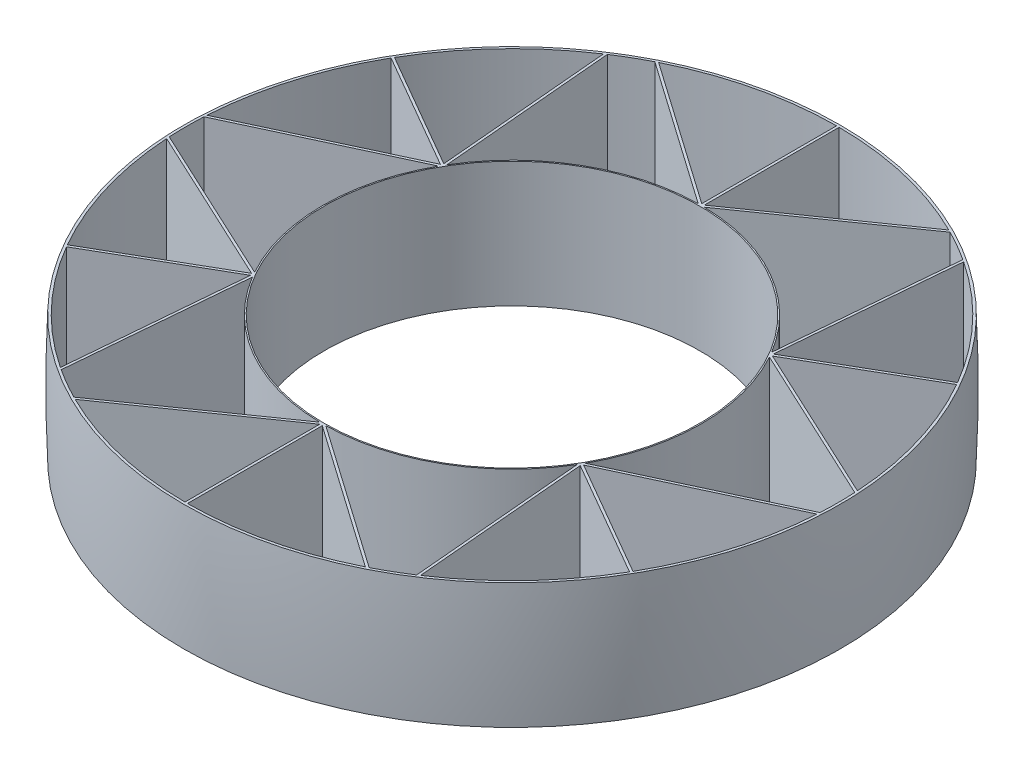
SolidWorks part; units mm, degrees
material "Бутил"
ref_plane "Спереди" through (0, 0, 0) normal (0, 0, 1) x (1, 0, 0)
ref_plane "Сверху" through (0, 0, 0) normal (0, 1, 0) x (1, 0, 0)
ref_plane "Справа" through (0, 0, 0) normal (1, 0, 0) x (0, 0, -1)
sketch "Эскиз3" plane through (0, 0, 0) normal (0, 1, 0) x (1, 0, 0)
  circle A0 centre (0, 0) radius 130
  circle A1 centre (0, 0) radius 131
  dimension "D1" = 262
  dimension "D2" = 260
sketch "Эскиз6" plane through (0, 0, 0) normal (0, 1, 0) x (1, 0, 0)
  circle A0 centre (0, 0) radius 75
  circle A1 centre (0, 0) radius 75.5
  dimension "D1" = 150
  dimension "D2" = 151
extrude "Бобышка-Вытянуть9" add sketch "Эскиз6" along normal blind 50 contours A1 A0 region at (-75.2865, 0, 0)
extrude "Бобышка-Вытянуть10" add sketch "Эскиз3" along normal up to surface (50 mm away) up to face at (0, 50, 75)
sketch "Эскиз7" plane through (0, 0, 0) normal (0, 1, 0) x (1, 0, 0)
  line L1 (-0.5, -75.4983) -> (-0.5, -129.999)
  line L2 (0.5, -75.4983) -> (0.5, -129.999)
  line L3 (0, -130) -> (0, 0) construction
  circle A0 centre (0, 0) radius 75.5 construction
  arc A2 (-0.5, -75.4983) -> (0.5, -75.4983) centre (0, -48.3147) ccw
  arc A3 (-0.5, -129.999) -> (0.5, -129.999) centre (0, 0) ccw
  circle A5 centre (0, 0) radius 130 construction
  point P1 (0, -75.5029)
  dimension "D4" = 27.1883
  dimension "D1" = 1
extrude "Бобышка-Вытянуть11" add sketch "Эскиз7" along normal up to surface (50 mm away) up to face at (0, 50, 75)
sketch "Эскиз4" plane through (0, 0, 0) normal (0, -1, 0) x (1, 0, 0)
  line L2 (-58.899, 115.8918) -> (-1.2, 75.4905)
  line L4 (0.5, 129.999) -> (0.5, 75.4983) construction
  line L6 (0, 148.9306) -> (0, 117.9564) construction
  line L7 (58.899, 115.8918) -> (1.2, 75.4905)
  line L8 (0.5, 76.1983) -> (57.9032, 116.3925)
  line L9 (0.5, 75.4983) -> (0.5, 76.1983)
  line L10 (-0.5, 76.1983) -> (-57.9032, 116.3925)
  line L11 (-0.5, 75.4983) -> (-0.5, 76.1983)
  circle A0 centre (0, 0) radius 130 construction
  arc A4 (1.2, 75.4905) -> (0.5, 75.4983) centre (0, 0) ccw
  arc A5 (57.9032, 116.3925) -> (58.899, 115.8918) centre (0, 0) cw
  circle A6 centre (0, 0) radius 75.5 construction
  arc A7 (-0.5, 129.999) -> (0.5, 129.999) centre (0, 0) ccw construction
  arc A8 (-57.9032, 116.3925) -> (-58.899, 115.8918) centre (0, 0) ccw
  arc A9 (-1.2, 75.4905) -> (-0.5, 75.4983) centre (0, 0) cw
  point P2 (0, 0)
  dimension "D1" = 110
  dimension "D5" = 0.7
  dimension "D6" = 0.7
extrude "Бобышка-Вытянуть12" add sketch "Эскиз4" against normal up to surface (50 mm away) up to face at (0, 50, 75)
sketch "Эскиз5" plane through (0, 0, 0) normal (1, 0, 0) x (0, 0, -1)
  line L0 (-131, 0) -> (-131, 50)
  line L2 (-156.6734, 25) -> (-131.9727, 25) construction
  line L4 (-131, 50) -> (-131, 0)
  line L5 (-131, 25) -> (-131, 50)
  line L7 (-131, 0) -> (-131, 50)
  line L8 (0, 0) -> (0, 64.3857) construction
  arc A3 (-131, 50) -> (-131, 0) centre (468.4789, 25) ccw
  dimension "D1" = 600
revolve "Повернуть2" add sketch "Эскиз5" angle 360 about L8 region at (0, 25, 131.2084)
pattern_circular "Круговой массив9" count 6 over 360 about axis through (0, 50, 0) along (0, -1, 0) of "Бобышка-Вытянуть12" reverse direction yes
pattern_circular "Круговой массив10" count 6 over 360 about axis through (0, 50, 0) along (0, -1, 0) of "Бобышка-Вытянуть11" reverse direction yes
